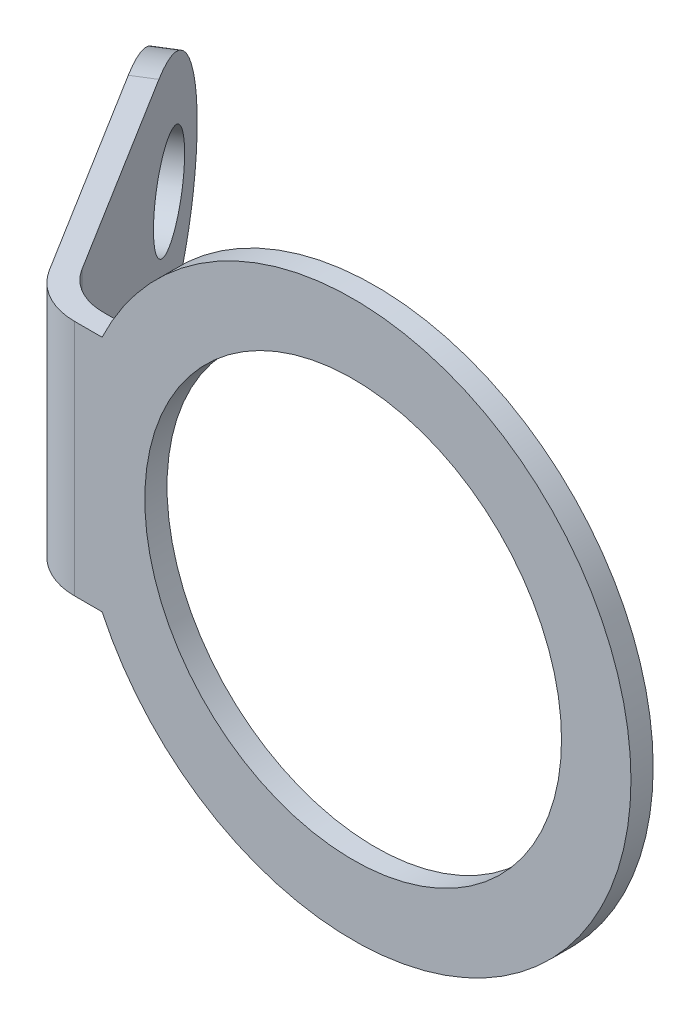
SolidWorks part; units mm, degrees
ref_plane "Front Plane" through (0, 0, 0) normal (0, 0, 1) x (1, 0, 0)
ref_plane "Top Plane" through (0, 0, 0) normal (0, 1, 0) x (1, 0, 0)
ref_plane "Right Plane" through (0, 0, 0) normal (1, 0, 0) x (0, 0, -1)
sketch "Sketch1" plane through (0, 0, 0) normal (0, 0, 1) x (1, 0, 0)
  circle A0 centre (0, 0) radius 6.35
  circle A1 centre (0, 0) radius 4.7625
extrude "Extrude1" add sketch "Sketch1" along normal blind 0.508
sketch "Sketch2" plane through (0, 0, 0) normal (0, 1, 0) x (1, 0, 0)
  line L0 (-6.35, -0.508) -> (-6.35, 0)
  line L1 (-7.3675, -0.268) -> (-12.0586, 7.286)
  line L2 (-6.936, -0.508) -> (-7.2185, -0.508)
  line L3 (-7.3675, -0.268) -> (-7.2185, -0.508)
  line L4 (-6.35, 0) -> (-6.936, 0)
  line L5 (-11.627, 7.554) -> (-12.0586, 7.286)
  line L6 (-6.936, -0.508) -> (-6.35, -0.508)
  line L7 (-6.936, 0) -> (-11.627, 7.554)
  dimension "D1" = 0.508
extrude "Extrude2" add sketch "Sketch2" along normal blind 2.7178 and the other way blind 2.7178
sketch "Sketch3" plane through (0, 0, 0.508) normal (0, 0, 1) x (1, 0, 0)
  line L0 (-6.35, 2.7178) -> (-5.739, 2.7178)
  line L1 (-5.739, 2.7178) -> (-5.739, -2.7178)
  line L2 (-5.739, -2.7178) -> (-6.35, -2.7178)
  line L3 (-6.35, -2.7178) -> (-6.35, 2.7178)
  circle A0 centre (0, 0) radius 6.35 construction
extrude "Extrude3" add sketch "Sketch3" against normal blind 0.508
fillet "Fillet1" radius 1.27 1 edges at (-6.936, 0, 0)
fillet "Fillet2" radius 1.524 1 edges at (-7.2185, 0, 0.508)
fillet "Fillet3" radius 2.7178 2 edges at (-11.8428, 2.7178, -7.42) (-11.8428, -2.7178, -7.42)
hole_wizard "1/32 (0.03125) Diameter Hole1" positions "3DSketch1" profile "Sketch4" hole size "1/32" standard "Ansi Inch"
sketch3d "3DSketch1"
  point P0 (-11.0044, 0, -5.5885)
sketch "Sketch4" plane through (-11.0044, 0, -5.5885) normal (0, 1, 0) x (0.5276, 0, 0.8495)
  line L0 (0, 0) -> (0, 6.35)
  line L1 (0, 6.35) -> (1.1049, 6.35)
  line L2 (1.1049, 6.35) -> (1.1049, 0)
  line L5 (1.1049, 0) -> (0, 0)
  line L10 (0, 6.35) -> (-1.1049, 6.35) construction
  line L11 (0, -6.35) -> (0, 107.95) construction
  dimension "Hole Dia." = 2.2098
  dimension "Hole Depth" = 6.35
  dimension "Drill Angle" = 180
